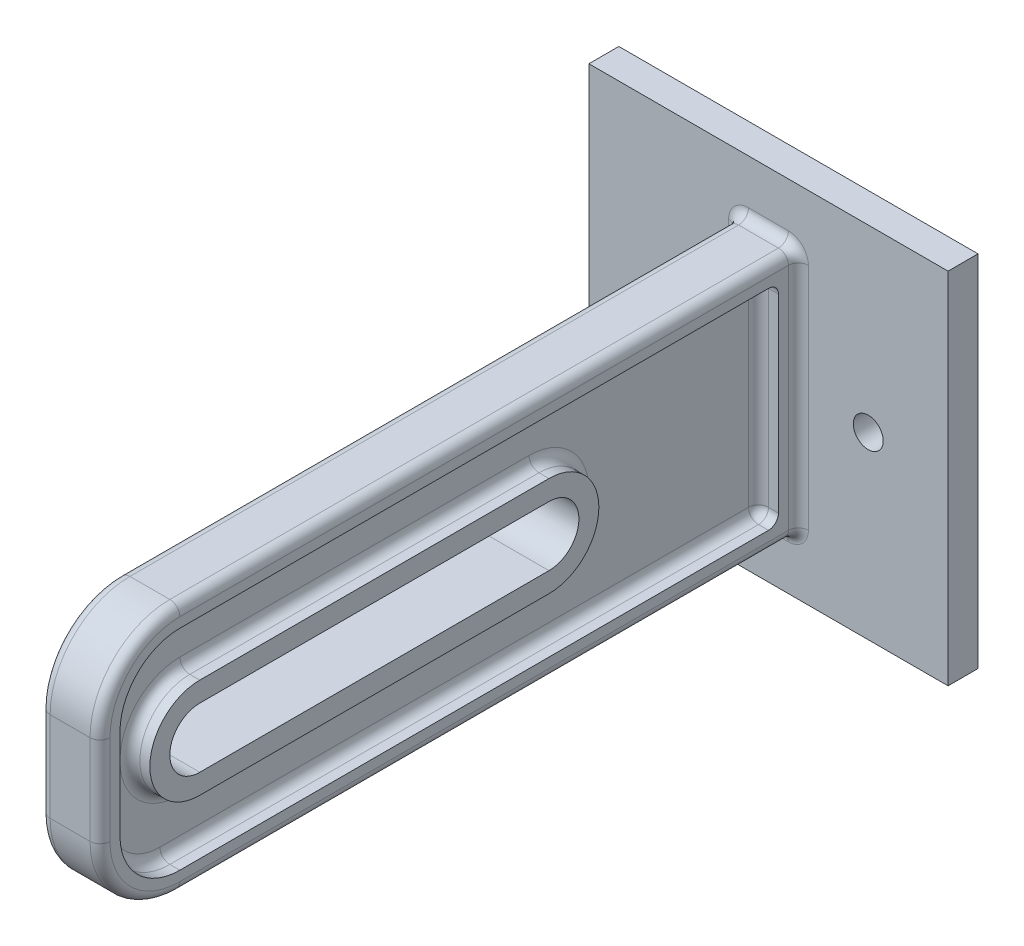
SolidWorks part; units mm, degrees
ref_plane "Front Plane" through (0, 0, 0) normal (0, 0, 1) x (1, 0, 0)
ref_plane "Top Plane" through (0, 0, 0) normal (0, 1, 0) x (1, 0, 0)
ref_plane "Right Plane" through (0, 0, 0) normal (1, 0, 0) x (0, 0, -1)
sketch "Sketch1" plane through (0, 0, 0) normal (0, 0, 1) x (1, 0, 0)
  line L1 (18, -18) -> (-18, -18)
  line L2 (18, -18) -> (18, 18)
  line L3 (18, 18) -> (-18, 18)
  line L4 (-18, -18) -> (-18, 18)
  line L5 (18, -18) -> (-18, 18) construction
  line L6 (18, 18) -> (-18, -18) construction
  point P0 (0, 0)
  dimension "D1" = 36
  dimension "D2" = 36
extrude "Boss-Extrude1" add sketch "Sketch1" along normal blind 3
sketch "Sketch3" plane through (0, 0, 3) normal (0, 0, 1) x (1, 0, 0)
  line L0 (-17.3978, 0) -> (16.6015, 0) construction
  line L1 (0, -8.6377) -> (0, 8.8214) construction
  circle A0 centre (-10, 0) radius 1.5
  circle A1 centre (10, 0) radius 1.5
  dimension "D1" = 3
  dimension "D2" = 20
extrude "Cut-Extrude1" cut sketch "Sketch3" against normal through all
sketch "Sketch4" plane through (0, 0, 3) normal (0, 0, 1) x (1, 0, 0)
  line L1 (3, -12.5) -> (-3, -12.5)
  line L2 (3, -12.5) -> (3, 12.5)
  line L3 (3, 12.5) -> (-3, 12.5)
  line L4 (-3, -12.5) -> (-3, 12.5)
  line L5 (3, -12.5) -> (-3, 12.5) construction
  line L6 (3, 12.5) -> (-3, -12.5) construction
  point P0 (0, 0)
  dimension "D1" = 6
  dimension "D2" = 25
extrude "Boss-Extrude2" add sketch "Sketch4" along normal blind 70
sketch "Sketch5" plane through (-3, 0, 0) normal (-1, 0, 0) x (0, 0, 1)
  line L3 (28, 0) -> (63, 0) construction
  line L6 (28, 3) -> (63, 3)
  line L7 (28, -3) -> (63, -3)
  line L10 (73, 12.5) -> (73, -12.5) construction
  arc A4 (28, 3) -> (28, -3) centre (28, 0) ccw
  arc A5 (63, -3) -> (63, 3) centre (63, 0) ccw
  point P2 (45.5, 0)
  dimension "D1" = 10
  dimension "D3" = 3
  dimension "D2" = 35
extrude "Cut-Extrude2" cut sketch "Sketch5" against normal through all
fillet "Fillet1" radius 8 2 edges at (0, -12.5, 73) (0, 12.5, 73)
sketch "Sketch6" plane through (-3, 0, 0) normal (-1, 0, 0) x (0, 0, 1)
  line L109 (5, 10.5) -> (5, -10.5)
  line L110 (5, -10.5) -> (65, -10.5)
  line L111 (71, -4.5) -> (71, 4.5)
  line L112 (65, 10.5) -> (5, 10.5)
  line L113 (5, 10.5) -> (5, -10.5)
  line L114 (5, -10.5) -> (65, -10.5)
  line L115 (71, -4.5) -> (71, 4.5)
  line L116 (65, 10.5) -> (5, 10.5)
  line L121 (28, -5) -> (63, -5)
  line L122 (63, 5) -> (28, 5)
  line L123 (28, -5) -> (63, -5)
  line L124 (63, 5) -> (28, 5)
  arc A70 (65, -10.5) -> (71, -4.5) centre (65, -4.5) ccw
  arc A71 (71, 4.5) -> (65, 10.5) centre (65, 4.5) ccw
  arc A72 (65, -10.5) -> (71, -4.5) centre (65, -4.5) ccw
  arc A73 (71, 4.5) -> (65, 10.5) centre (65, 4.5) ccw
  arc A78 (28, 5) -> (28, -5) centre (28, 0) ccw
  arc A79 (63, -5) -> (63, 5) centre (63, 0) ccw
  arc A80 (28, 5) -> (28, -5) centre (28, 0) ccw
  arc A81 (63, -5) -> (63, 5) centre (63, 0) ccw
  dimension "D1" = 2
  dimension "D2" = 2
extrude "Cut-Extrude3" cut sketch "Sketch6" against normal blind 2
mirror "Mirror1" about plane through (0, 0, 0) normal (1, 0, 0) of "Cut-Extrude3"
fillet "Fillet2" radius 1 14 edges at (3, 12.5, 34) (3, 10.1569, 70.6569) (3, 0, 73) (3, -10.1569, 70.6569) (3, -12.5, 34) (-3, -10.1569, 70.6569) (-3, 0, 73) (-3, 10.1569, 70.6569) (-3, 12.5, 34) (-3, -12.5, 34) (0, 12.5, 3) (3, 0, 3) (0, -12.5, 3) (-3, 0, 3)
fillet "Fillet3" radius 1 8 edges at (1, 5, 45.5) (1, 0, 68) (1, -5, 45.5) (1, 0, 23) (-1, 0, 68) (-1, 5, 45.5) (-1, 0, 23) (-1, -5, 45.5)
fillet "Fillet4" radius 1 12 edges at (1, 0, 5) (1, 0, 71) (1, 8.7426, 69.2426) (1, 10.5, 35) (1, -8.7426, 69.2426) (1, -10.5, 35) (-1, 0, 71) (-1, -8.7426, 69.2426) (-1, -10.5, 35) (-1, 8.7426, 69.2426) (-1, 10.5, 35) (-1, 0, 5)
fillet "Fillet5" radius 1 8 edges at (2.5, 10.5, 5) (2.5, -10.5, 5) (-2.5, 10.5, 5) (-2.5, -10.5, 5) (1.2929, 10.2071, 5.2929) (1.2929, -10.2071, 5.2929) (-1.2929, 10.2071, 5.2929) (-1.2929, -10.2071, 5.2929)
